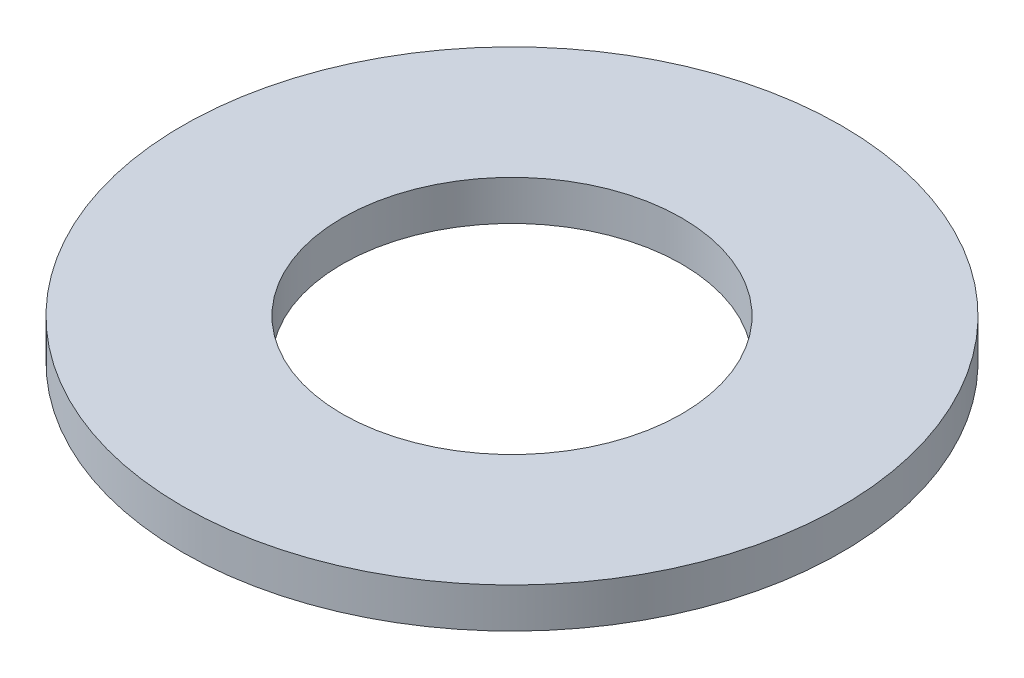
SolidWorks part; units mm, degrees
ref_plane "Front Plane" through (0, 0, 0) normal (0, 0, 1) x (1, 0, 0)
ref_plane "Top Plane" through (0, 0, 0) normal (0, 1, 0) x (1, 0, 0)
ref_plane "Right Plane" through (0, 0, 0) normal (1, 0, 0) x (0, 0, -1)
sketch "Sketch1" plane through (0, 0, 0) normal (0, 1, 0) x (1, 0, 0)
  circle A0 centre (0, 0) radius 82.5
  dimension "FLANGE_OD" = 165
extrude "Boss-Extrude1" add sketch "Sketch1" along normal blind 10
sketch "Sketch2" plane through (0, 0, 0) normal (0, 1, 0) x (1, 0, 0)
  circle A0 centre (0, 0) radius 42.5
  dimension "BORE_D" = 85
extrude "Cut-Extrude1" cut sketch "Sketch2" along normal through all
sketch "Sketch3" plane through (0, 10, 0) normal (0, 1, 0) x (1, 0, 0)
  circle A0 centre (0, 0) radius 25.3713 construction
  circle A1 centre (-25.3713, 0) radius 5.6221
  dimension "BOLT_D" = 11.2442
  dimension "BOLT_PCD" = 50.7425
extrude "Cut-Extrude2" cut sketch "Sketch3" against normal blind 8.7135 rebuild error yes
pattern_circular "CirPattern1" count 8 over 360 rebuild error yes
